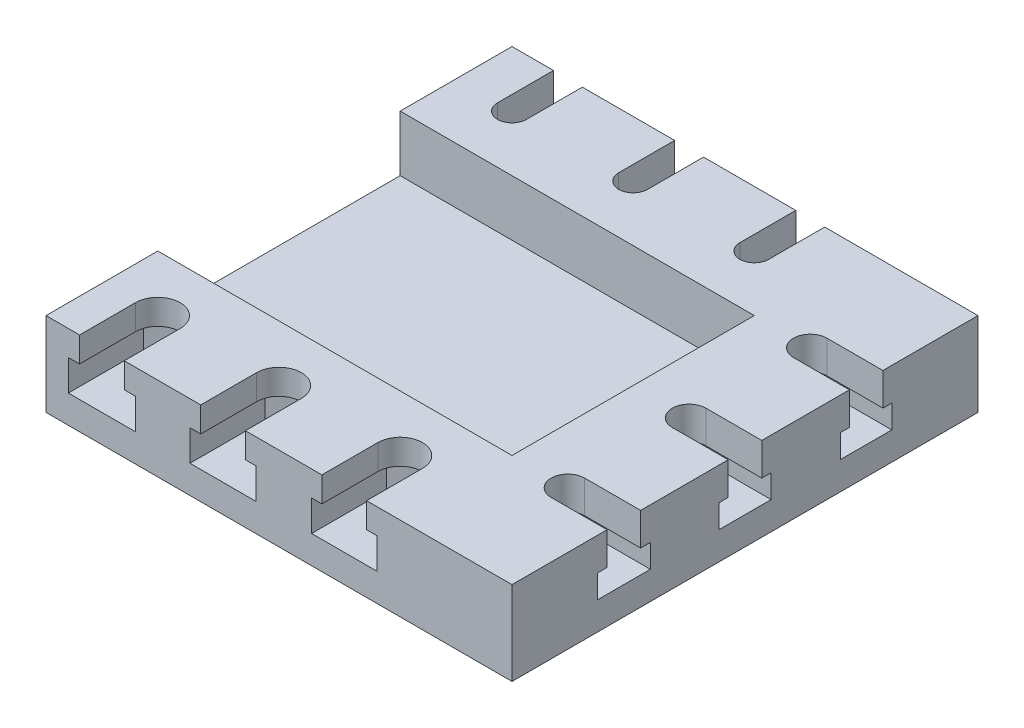
SolidWorks part; units mm, degrees
ref_plane "Front Plane" through (0, 0, 0) normal (0, 0, 1) x (1, 0, 0)
ref_plane "Top Plane" through (0, 0, 0) normal (0, 1, 0) x (1, 0, 0)
ref_plane "Right Plane" through (0, 0, 0) normal (1, 0, 0) x (0, 0, -1)
sketch "Sketch1" plane through (0, 0, 0) normal (0, 1, 0) x (1, 0, 0)
  line L1 (-25, 25) -> (25, 25)
  line L2 (-25, 25) -> (-25, -25)
  line L3 (-25, -25) -> (25, -25)
  line L4 (25, 25) -> (25, -25)
  line L5 (-25, 25) -> (25, -25) construction
  line L6 (-25, -25) -> (25, 25) construction
  point P0 (0, 0)
  dimension "D1" = 50
  dimension "D2" = 50
extrude "Boss-Extrude1" add sketch "Sketch1" along normal blind 3
sketch "Sketch2" plane through (0, 3, 0) normal (0, 1, 0) x (1, 0, 0)
  line L0 (-13, 13) -> (-25, 13)
  line L3 (-25, 25) -> (25, 25)
  line L6 (-25, 25) -> (-25, 13)
  line L11 (-25, -25) -> (25, -25)
  line L12 (25, 25) -> (25, -25)
  line L13 (-25, 25) -> (25, -25) construction
  line L14 (-25, -25) -> (25, 25) construction
  line L15 (-13, 13) -> (13, 13)
  line L17 (-13, -13) -> (13, -13)
  line L18 (13, 13) -> (13, -13)
  line L19 (-13, 13) -> (13, -13) construction
  line L20 (-13, -13) -> (13, 13) construction
  line L21 (-13, -13) -> (-25, -13)
  line L22 (-25, -13) -> (-25, -25)
  point P0 (0, 0)
  point P5 (0, 0)
  dimension "D1" = 26
extrude "Boss-Extrude2" add sketch "Sketch2" along normal blind 6
sketch "Sketch3" plane through (0, 3, 0) normal (0, 1, 0) x (1, 0, 0)
  line L0 (-25, 25) -> (-25, 13) construction
  line L3 (-21.5, 20.4434) -> (-21.5, 17.5566)
  line L4 (-21.5, 17.5566) -> (-19, 16.1132)
  line L5 (-19, 16.1132) -> (-16.5, 17.5566)
  line L6 (-16.5, 17.5566) -> (-16.5, 20.4434)
  line L8 (-6, 16.0555) -> (-3.45, 17.5278)
  line L9 (-3.45, 17.5278) -> (-3.45, 20.4722)
  line L12 (-8.55, 20.4722) -> (-8.55, 17.5278)
  line L13 (-8.55, 17.5278) -> (-6, 16.0555)
  line L14 (7, 15.9978) -> (9.6, 17.4989)
  line L15 (9.6, 17.4989) -> (9.6, 20.5011)
  line L18 (4.4, 20.5011) -> (4.4, 17.4989)
  line L19 (4.4, 17.4989) -> (7, 15.9978)
  line L21 (20.5877, 15.75) -> (17.4123, 15.75)
  line L22 (17.4123, 15.75) -> (15.8246, 13)
  line L23 (15.8246, 13) -> (17.4123, 10.25)
  line L24 (17.4123, 10.25) -> (20.5877, 10.25)
  line L27 (20.6166, 2.8) -> (17.3834, 2.8)
  line L28 (17.3834, 2.8) -> (15.7668, 0)
  line L29 (15.7668, 0) -> (17.3834, -2.8)
  line L30 (17.3834, -2.8) -> (20.6166, -2.8)
  line L33 (20.6454, -10.15) -> (17.3546, -10.15)
  line L34 (17.3546, -10.15) -> (15.7091, -13)
  line L35 (15.7091, -13) -> (17.3546, -15.85)
  line L36 (17.3546, -15.85) -> (20.6454, -15.85)
  line L39 (10.5, -21.0207) -> (10.5, -16.9793)
  line L40 (10.5, -16.9793) -> (7, -14.9585)
  line L41 (7, -14.9585) -> (3.5, -16.9793)
  line L42 (3.5, -16.9793) -> (3.5, -21.0207)
  line L45 (-2.45, -21.0496) -> (-2.45, -16.9504)
  line L46 (-2.45, -16.9504) -> (-6, -14.9008)
  line L47 (-6, -14.9008) -> (-9.55, -16.9504)
  line L48 (-9.55, -16.9504) -> (-9.55, -21.0496)
  line L51 (-15.4, -21.0785) -> (-15.4, -16.9215)
  line L52 (-15.4, -16.9215) -> (-19, -14.8431)
  line L53 (-19, -14.8431) -> (-22.6, -16.9215)
  line L54 (-22.6, -16.9215) -> (-22.6, -21.0785)
  line L56 (-21.5, 20.4434) -> (-21.5, 25)
  line L57 (-16.5, 20.4434) -> (-16.5, 25)
  line L58 (-21.5, 25) -> (-16.5, 25)
  line L60 (-8.55, 20.4722) -> (-8.55, 25)
  line L61 (-3.45, 20.4722) -> (-3.45, 25)
  line L62 (-8.55, 25) -> (-3.45, 25)
  line L64 (4.4, 20.5011) -> (4.4, 25)
  line L65 (9.6, 20.5011) -> (9.6, 25)
  line L66 (4.4, 25) -> (9.6, 25)
  line L68 (20.5877, 15.75) -> (25, 15.75)
  line L69 (20.5877, 10.25) -> (25, 10.25)
  line L70 (25, 15.75) -> (25, 10.25)
  line L72 (20.6166, 2.8) -> (25, 2.8)
  line L73 (20.6166, -2.8) -> (25, -2.8)
  line L74 (25, 2.8) -> (25, -2.8)
  line L76 (20.6454, -10.15) -> (25, -10.15)
  line L77 (20.6454, -15.85) -> (25, -15.85)
  line L78 (25, -10.15) -> (25, -15.85)
  line L80 (3.5, -21.0207) -> (3.5, -25)
  line L81 (10.5, -21.0207) -> (10.5, -25)
  line L82 (3.5, -25) -> (10.5, -25)
  line L84 (-9.55, -21.0496) -> (-9.55, -25)
  line L85 (-2.45, -21.0496) -> (-2.45, -25)
  line L86 (-9.55, -25) -> (-2.45, -25)
  line L88 (-22.6, -21.0785) -> (-22.6, -25)
  line L89 (-15.4, -21.0785) -> (-15.4, -25)
  line L90 (-22.6, -25) -> (-15.4, -25)
  line L91 (-25, -25) -> (25, -25) construction
  line L92 (25, -25) -> (25, 25) construction
  line L93 (25, 25) -> (-25, 25) construction
  line L95 (-19, 21.8868) -> (-20.25, 21.1651) [skipped]
  line L96 (-16.5, 20.4434) -> (-17.75, 21.1651) [skipped]
  line L97 (-6, 21.9445) -> (-7.275, 21.2084) [skipped]
  line L98 (-3.45, 20.4722) -> (-4.725, 21.2084) [skipped]
  line L99 (7, 22.0022) -> (5.7, 21.2517) [skipped]
  line L100 (9.6, 20.5011) -> (8.3, 21.2517) [skipped]
  line L101 (22.1754, 13) -> (21.3816, 14.375) [skipped]
  line L102 (20.5877, 10.25) -> (21.3816, 11.625) [skipped]
  line L103 (22.2332, 0) -> (21.4249, 1.4) [skipped]
  line L104 (20.6166, -2.8) -> (21.4249, -1.4) [skipped]
  line L105 (22.2909, -13) -> (21.4682, -11.575) [skipped]
  line L106 (20.6454, -15.85) -> (21.4682, -14.425) [skipped]
  line L107 (5.25, -22.0311) -> (7, -23.0415) [skipped]
  line L108 (8.75, -22.0311) -> (10.5, -21.0207) [skipped]
  line L109 (-7.775, -22.0744) -> (-6, -23.0992) [skipped]
  line L110 (-4.225, -22.0744) -> (-2.45, -21.0496) [skipped]
  line L111 (-20.8, -22.1177) -> (-19, -23.1569) [skipped]
  line L112 (-17.2, -22.1177) -> (-15.4, -21.0785) [skipped]
  arc A0 (-21.5, 19) -> (-16.5, 19) centre (-19, 19) ccw construction
  arc A1 (-8.55, 19) -> (-3.45, 19) centre (-6, 19) ccw construction
  arc A2 (4.4, 19) -> (9.6, 19) centre (7, 19) ccw construction
  arc A3 (19, 15.75) -> (19, 10.25) centre (19, 13) ccw construction
  arc A4 (19, 2.8) -> (19, -2.8) centre (19, 0) ccw construction
  arc A5 (19, -10.15) -> (19, -15.85) centre (19, -13) ccw construction
  arc A6 (10.5, -19) -> (3.5, -19) centre (7, -19) ccw construction
  arc A7 (-2.45, -19) -> (-9.55, -19) centre (-6, -19) ccw construction
  arc A8 (-15.4, -19) -> (-22.6, -19) centre (-19, -19) ccw construction
  point P0 (-19, 19)
  point P1 (-6, 19)
  point P2 (7, 19)
  point P3 (19, 13)
  point P4 (19, 0)
  point P5 (19, -13)
  point P6 (-19, -19)
  point P7 (-6, -19)
  point P8 (7, -19)
  point P77 (-15.4, -25)
  point P105 (-2.45, -25)
  point P106 (10.5, -25)
  point P107 (25, -10.15)
  point P110 (25, 2.8)
  point P111 (25, 15.75)
  point P112 (-16.5, 25)
  point P115 (-8.55, 25)
  point P116 (9.6, 25)
  dimension "D1" = 19
  dimension "D2" = 19
  dimension "D3" = 19
  dimension "D4" = 13
  dimension "D5" = 13
  dimension "D6" = 13
  dimension "D7" = 13
  dimension "D8" = 13
  dimension "D9" = 13
  dimension "D10" = 6
  dimension "D11" = 5
  dimension "D12" = 5.1
  dimension "D13" = 5.2
  dimension "D14" = 5.5
  dimension "D15" = 5.6
  dimension "D16" = 5.7
  dimension "D17" = 7
  dimension "D18" = 7.1
  dimension "D19" = 7.2
extrude "Cut-Extrude1" cut sketch "Sketch3" along normal blind 2.1 contours L58 L56 L3 L4 L5 L6 L57 | L62 L60 L12 L13 L8 L9 L61 | L66 L64 L18 L19 L14 L15 L65 region at (-19, 3, -20.9068) region at (-6, 3, -20.8848) region at (7, 3, -20.8628)
extrude "Cut-Extrude2" cut sketch "Sketch3<3>" along normal blind 2.5 contours L70 L68 L21 L22 L23 L24 L69 | L74 L72 L27 L28 L29 L30 L73 | L78 L76 L33 L34 L35 L36 L77 region at (20.7967, 3, -13) region at (20.7746, 3, 0) region at (20.7526, 3, 13)
sketch "Sketch3<3>" plane through (0, 3, 0) normal (0, 1, 0) x (1, 0, 0) same geometry as "Sketch3"
extrude "Cut-Extrude3" cut sketch "Sketch3<4>" along normal blind 3.3 contours L88 L90 L89 L51 L52 L53 L54 | L84 L86 L85 L45 L46 L47 L48 | L80 L82 L81 L39 L40 L41 L42 region at (7, 3, 20.4656) region at (-6, 3, 20.4435) region at (-19, 3, 20.4214)
sketch "Sketch3<4>" plane through (0, 3, 0) normal (0, 1, 0) x (1, 0, 0) same geometry as "Sketch3"
sketch "Sketch4" plane through (0, 9, 0) normal (0, 1, 0) x (1, 0, 0)
  circle A0 centre (-19, 19) radius 1.55
  circle A1 centre (-6, 19) radius 1.55
  circle A2 centre (7, 19) radius 1.55
  circle A3 centre (19, 13) radius 1.8
  circle A4 centre (19, 0) radius 1.8
  circle A5 centre (19, -13) radius 1.8
  circle A6 centre (7, -19) radius 2.4
  circle A7 centre (-6, -19) radius 2.4
  circle A8 centre (-19, -19) radius 2.4
  dimension "D1" = 3.1
  dimension "D2" = 3.1
  dimension "D3" = 3.1
  dimension "D4" = 3.6
  dimension "D5" = 3.6
  dimension "D6" = 3.6
  dimension "D7" = 4.8
  dimension "D8" = 4.8
  dimension "D9" = 4.8
extrude "Cut-Extrude4" cut sketch "Sketch4" against normal through all
sketch "Sketch5" plane through (0, 9, 0) normal (0, 1, 0) x (1, 0, 0)
  line L0 (25, 25) -> (-25, 25) construction
  line L1 (-17.45, 19) -> (-20.55, 19)
  line L2 (-17.45, 19) -> (-17.45, 25)
  line L3 (-17.45, 25) -> (-20.55, 25)
  line L4 (-20.55, 19) -> (-20.55, 25)
  line L5 (25, -25) -> (25, 25) construction
  line L6 (-7.55, 19) -> (-4.45, 19)
  line L7 (-7.55, 19) -> (-7.55, 25)
  line L8 (-7.55, 25) -> (-4.45, 25)
  line L9 (-4.45, 19) -> (-4.45, 25)
  line L10 (5.45, 19) -> (8.55, 19)
  line L11 (5.45, 19) -> (5.45, 25)
  line L12 (5.45, 25) -> (8.55, 25)
  line L13 (8.55, 19) -> (8.55, 25)
  line L14 (19, 14.8) -> (25, 14.8)
  line L15 (19, 14.8) -> (19, 11.2)
  line L16 (19, 11.2) -> (25, 11.2)
  line L17 (25, 14.8) -> (25, 11.2)
  line L18 (-25, -25) -> (25, -25) construction
  line L19 (19, 1.8) -> (25, 1.8)
  line L20 (19, 1.8) -> (19, -1.8)
  line L21 (19, -1.8) -> (25, -1.8)
  line L22 (25, 1.8) -> (25, -1.8)
  line L23 (19, -11.2) -> (25, -11.2)
  line L24 (19, -11.2) -> (19, -14.8)
  line L25 (19, -14.8) -> (25, -14.8)
  line L26 (25, -11.2) -> (25, -14.8)
  line L27 (4.6, -19) -> (9.4, -19)
  line L28 (4.6, -19) -> (4.6, -25)
  line L29 (4.6, -25) -> (9.4, -25)
  line L30 (9.4, -19) -> (9.4, -25)
  line L32 (-8.4, -19) -> (-3.6, -19)
  line L33 (-8.4, -19) -> (-8.4, -25)
  line L34 (-8.4, -25) -> (-3.6, -25)
  line L35 (-3.6, -19) -> (-3.6, -25)
  line L36 (-16.6, -19) -> (-21.4, -19)
  line L37 (-16.6, -19) -> (-16.6, -25)
  line L38 (-16.6, -25) -> (-21.4, -25)
  line L39 (-21.4, -19) -> (-21.4, -25)
  circle A0 centre (-19, 19) radius 1.55 construction
  circle A1 centre (-6, 19) radius 1.55 construction
  circle A2 centre (7, 19) radius 1.55 construction
  circle A3 centre (19, 13) radius 1.8 construction
  circle A4 centre (19, 0) radius 1.8 construction
  circle A5 centre (19, -13) radius 1.8 construction
  circle A6 centre (7, -19) radius 2.4 construction
  circle A7 centre (-6, -19) radius 2.4 construction
  circle A8 centre (-19, -19) radius 2.4 construction
extrude "Cut-Extrude5" cut sketch "Sketch5" against normal up to surface (6 mm away) up to face at (-19, 3, 21.4)
equation "\"D9@Sketch3\"=\"D4@Sketch3\""
equation "\"D8@Sketch3\"=\"D4@Sketch3\""
equation "\"D7@Sketch3\"=\"D4@Sketch3\""
equation "\"D6@Sketch3\"=\"D4@Sketch3\""
equation "\"D5@Sketch3\"=\"D4@Sketch3\""
